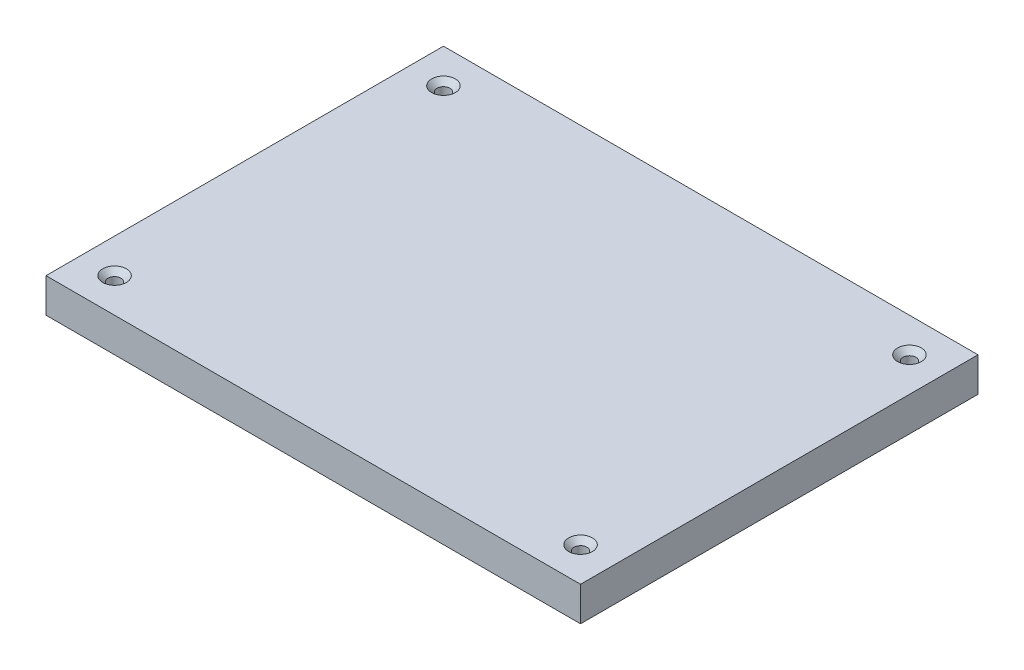
SolidWorks part; units mm, degrees
ref_plane "Front Plane" through (0, 0, 0) normal (0, 0, 1) x (1, 0, 0)
ref_plane "Top Plane" through (0, 0, 0) normal (0, 1, 0) x (1, 0, 0)
ref_plane "Right Plane" through (0, 0, 0) normal (1, 0, 0) x (0, 0, -1)
sketch "Sketch1" plane through (0, 0, 0) normal (0, 1, 0) x (1, 0, 0)
  line L1 (-49.53, -36.83) -> (49.53, -36.83)
  line L2 (-49.53, -36.83) -> (-49.53, 36.83)
  line L3 (-49.53, 36.83) -> (49.53, 36.83)
  line L4 (49.53, -36.83) -> (49.53, 36.83)
  line L5 (-49.53, -36.83) -> (49.53, 36.83) construction
  line L6 (-49.53, 36.83) -> (49.53, -36.83) construction
  point P0 (0, 0)
  dimension "D1" = 99.06
  dimension "D2" = 73.66
extrude "Boss-Extrude1" add sketch "Sketch1" along normal blind 6.35
sketch "Sketch2" plane through (0, 6.35, 0) normal (0, 1, 0) x (1, 0, 0)
  line L0 (49.53, 36.83) -> (-49.53, 36.83) construction
  line L1 (-43.18, -30.48) -> (43.18, -30.48) construction
  line L2 (-43.18, -30.48) -> (-43.18, 30.48) construction
  line L3 (-43.18, 30.48) -> (43.18, 30.48) construction
  line L4 (43.18, -30.48) -> (43.18, 30.48) construction
  line L5 (-43.18, -30.48) -> (43.18, 30.48) construction
  line L6 (-43.18, 30.48) -> (43.18, -30.48) construction
  line L7 (-49.53, 36.83) -> (-49.53, -36.83) construction
  point P0 (0, 0)
  point P11 (-43.18, 30.48)
  point P12 (-43.18, -30.48)
  point P13 (43.18, -30.48)
  point P14 (43.18, 30.48)
  dimension "D1" = 6.35
  dimension "D2" = 6.35
hole_wizard "CSK for M2 Flat Head Machine Screw1" positions "Sketch5" profile "Sketch7" countersink size "M2" standard "ANSI Metric" end condition through all
sketch "Sketch5" plane through (0, 6.35, 0) normal (0, 1, 0) x (1, 0, 0)
  point P0 (-43.18, 30.48)
  point P3 (-43.18, -30.48)
  point P6 (43.18, -30.48)
  point P9 (43.18, 30.48)
sketch "Sketch7" plane through (-43.18, 6.35, -30.48) normal (1, 0, 0) x (0, 0, 1)
  line L0 (0, 0) -> (0, 6.35)
  line L1 (0, 6.35) -> (1.2, 6.35)
  line L2 (1.2, 6.35) -> (1.2, 1)
  line L3 (1.2, 1) -> (2.2, 0)
  line L5 (2.2, 0) -> (0, 0)
  line L6 (-1.2, 1) -> (-2.2, 0) construction
  line L11 (0, -6.35) -> (0, 107.95) construction
  dimension "Thru Hole Dia." = 2.4
  dimension "Thru Hole Depth" = 6.35
  dimension "Near C'Sink Dia." = 4.4
  dimension "Near C'Sink Angle" = 90
shell "Shell1" thickness 4.7625 removed face at (-43.18, 0, -29.28)
equation "\"D2@Sketch2\"=\"D1@Sketch2\""
